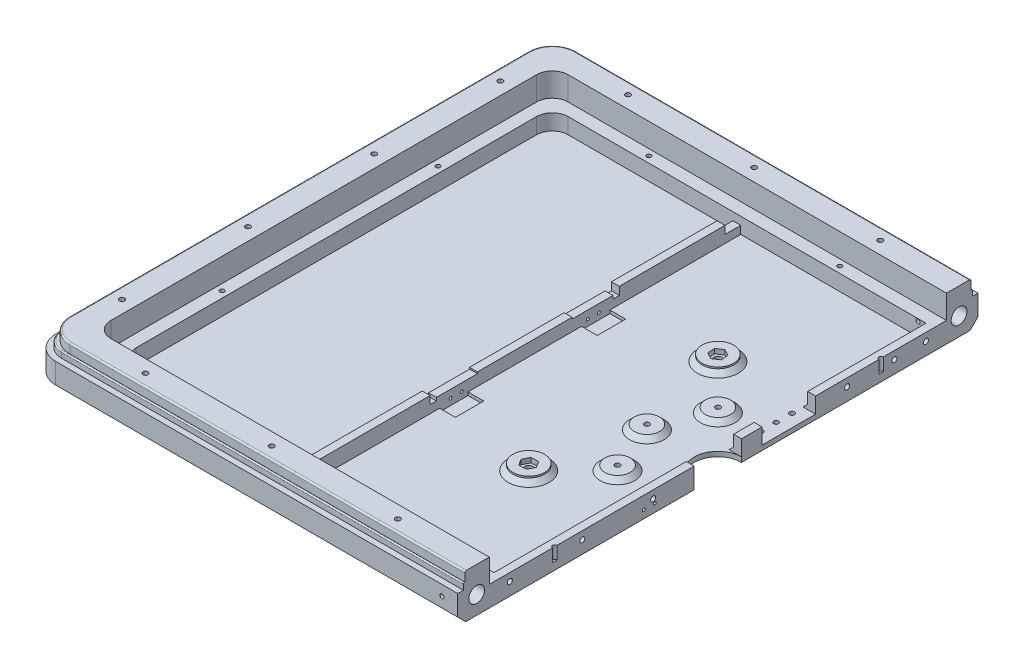
SolidWorks part; units mm, degrees
ref_plane "Front Plane" through (0, 0, 0) normal (0, 0, 1) x (1, 0, 0)
ref_plane "Top Plane" through (0, 0, 0) normal (0, 1, 0) x (1, 0, 0)
ref_plane "Right Plane" through (0, 0, 0) normal (1, 0, 0) x (0, 0, -1)
sketch "Sketch1" plane through (0, 0, 0) normal (0, 1, 0) x (1, 0, 0)
  line L1 (-270, -165) -> (270, -165)
  line L2 (-270, -165) -> (-270, 165)
  line L3 (-270, 165) -> (270, 165)
  line L4 (270, -165) -> (270, 165)
  line L5 (-270, -165) -> (270, 165) construction
  line L6 (-270, 165) -> (270, -165) construction
  point P0 (0, 0)
  dimension "D1" = 540
  dimension "D2" = 330
extrude "Boss-Extrude1" add sketch "Sketch1" along normal blind 3
sketch "Sketch2" plane through (0, 3, 0) normal (0, 1, 0) x (1, 0, 0)
  line L0 (250, 145) -> (-250, 145)
  line L1 (270, -165) -> (-270, -165)
  line L2 (270, -165) -> (270, 165)
  line L3 (270, 165) -> (-270, 165)
  line L4 (-270, -165) -> (-270, 165)
  line L5 (270, -165) -> (-270, 165) construction
  line L6 (270, 165) -> (-270, -165) construction
  line L7 (-250, -145) -> (-250, 145)
  line L8 (250, -145) -> (-250, -145)
  line L9 (250, -145) -> (250, 145)
  point P0 (0, 0)
  dimension "D1" = 20
  dimension "D2" = 540
extrude "Boss-Extrude2" add sketch "Sketch2" along normal blind 25 contours L0 L7 L8 L9 | L2 L1 L4 L3
fillet "Fillet1" radius 15 4 edges at (-270, 14, -165) (-270, 14, 165) (270, 14, 165) (270, 14, -165)
sketch "Sketch4" plane through (0, 28, 0) normal (0, 1, 0) x (1, 0, 0)
  line L0 (-270, 0) -> (-258, 0) construction
  line L1 (-270, -150) -> (-270, 150) construction
  line L2 (-258, 0) -> (-258, 40) construction
  line L3 (-258, 40) -> (-258, 120) construction
  line L4 (0, 0) -> (0, 145) construction
  line L5 (250, 145) -> (-250, 145) construction
  line L6 (0, 165) -> (0, 153) construction
  line L7 (255, 165) -> (-255, 165) construction
  line L8 (0, 153) -> (-50, 153) construction
  line L9 (-50, 153) -> (-130, 153) construction
  line L10 (-130, 153) -> (-210, 153) construction
  line L11 (130, 153) -> (210, 153) construction
  line L12 (50, 153) -> (130, 153) construction
  line L13 (258, 40) -> (258, 120) construction
  line L14 (0, 0) -> (78.1952, 0) construction
  line L15 (258, -40) -> (258, -120) construction
  line L16 (50, -153) -> (130, -153) construction
  line L17 (130, -153) -> (210, -153) construction
  line L18 (-130, -153) -> (-210, -153) construction
  line L19 (-50, -153) -> (-130, -153) construction
  line L20 (0, -153) -> (-50, -153) construction
  line L21 (0, -165) -> (0, -153) construction
  line L22 (-258, -40) -> (-258, -120) construction
  circle A0 centre (-258, 120) radius 1.6
  circle A1 centre (-258, 40) radius 1.6
  circle A2 centre (-210, 153) radius 1.6
  circle A3 centre (-130, 153) radius 1.6
  circle A4 centre (-50, 153) radius 1.6
  circle A5 centre (50, 153) radius 1.6
  circle A6 centre (130, 153) radius 1.6
  circle A7 centre (210, 153) radius 1.6
  circle A8 centre (258, 40) radius 1.6
  circle A9 centre (258, 120) radius 1.6
  circle A10 centre (258, -120) radius 1.6
  circle A11 centre (258, -40) radius 1.6
  circle A12 centre (210, -153) radius 1.6
  circle A13 centre (130, -153) radius 1.6
  circle A14 centre (50, -153) radius 1.6
  circle A15 centre (-50, -153) radius 1.6
  circle A16 centre (-130, -153) radius 1.6
  circle A17 centre (-210, -153) radius 1.6
  circle A18 centre (-258, -40) radius 1.6
  circle A19 centre (-258, -120) radius 1.6
  dimension "D1" = 50
  dimension "D2" = 80
  dimension "D3" = 80
  dimension "D4" = 12
  dimension "D5" = 12
  dimension "D6" = 40
  dimension "D7" = 80
extrude "Cut-Extrude1" cut sketch "Sketch4" against normal up to surface (28 mm away) up to face at (0, 0, 0)
sketch "Sketch5" plane through (0, 3, 0) normal (0, 1, 0) x (1, 0, 0)
  circle A0 centre (0, 0) radius 15
  dimension "D1" = 30
extrude "Cut-Extrude2" cut sketch "Sketch5" against normal up to surface (3 mm away) up to face at (-130, 0, 151.4)
chamfer "Chamfer1" distance 5 angle 45 8 edges at (270, 0, 0) (0, 0, -165) (0, 0, 165) (265.6066, 0, -160.6066) (265.6066, 0, 160.6066) (-265.6066, 0, -160.6066) (-265.6066, 0, 160.6066) (-270, 0, 0)
sketch "Sketch7" plane through (0, 0, 0) normal (0, -1, 0) x (1, 0, 0)
  line L1 (-60, -60) -> (60, -60) construction
  line L2 (-60, -60) -> (-60, 60) construction
  line L3 (-60, 60) -> (60, 60) construction
  line L4 (60, -60) -> (60, 60) construction
  line L5 (-60, -60) -> (60, 60) construction
  line L6 (-60, 60) -> (60, -60) construction
  circle A0 centre (-60, 60) radius 2.6
  circle A1 centre (60, 60) radius 2.6
  circle A2 centre (60, -60) radius 2.6
  circle A3 centre (-60, -60) radius 2.6
  point P0 (0, 0)
  dimension "D1" = 120
  dimension "D2" = 120
extrude "Cut-Extrude3" cut sketch "Sketch7" against normal up to surface (3 mm away) up to face at (0, 3, 15)
sketch "Sketch9" plane through (0, 0, 0) normal (0, -1, 0) x (1, 0, 0)
  line L0 (0, 0) -> (45, 0) construction
  line L1 (-31.8198, -31.8198) -> (31.8198, -31.8198) construction
  line L2 (-31.8198, -31.8198) -> (-31.8198, 31.8198) construction
  line L3 (-31.8198, 31.8198) -> (31.8198, 31.8198) construction
  line L4 (31.8198, -31.8198) -> (31.8198, 31.8198) construction
  line L5 (-31.8198, -31.8198) -> (31.8198, 31.8198) construction
  line L6 (-31.8198, 31.8198) -> (31.8198, -31.8198) construction
  line L7 (0, 0) -> (0, -31.8198) construction
  circle A0 centre (-31.8198, 31.8198) radius 1.6
  circle A1 centre (31.8198, 31.8198) radius 1.6
  circle A2 centre (31.8198, -31.8198) radius 1.6
  circle A3 centre (-31.8198, -31.8198) radius 1.6
  circle A4 centre (45, 0) radius 1.6
  circle A5 centre (-45, 0) radius 1.6
  point P0 (0, 0)
  dimension "D3" = 45
  dimension "D1" = 90
  dimension "D2" = 90
extrude "Cut-Extrude4" cut sketch "Sketch9" against normal blind 47
sketch "Sketch17" plane through (0, 28, 0) normal (0, 1, 0) x (1, 0, 0)
  line L0 (0, 0) -> (0, 165) construction
  line L1 (265, 165) -> (-265, 165) construction
sketch "Sketch18" plane through (0, 28, 0) normal (0, 1, 0) x (1, 0, 0)
  line L0 (0, 165) -> (0, -165) construction
  line L1 (265, 165) -> (-265, 165) construction
  line L2 (265, -165) -> (-265, -165) construction
sketch "Sketch19" plane through (0, 28, 0) normal (0, 1, 0) x (1, 0, 0)
  line L0 (250.5, 160.5) -> (-250.5, 160.5)
  line L1 (255, -165) -> (-255, -165)
  line L2 (270, -150) -> (270, 150)
  line L3 (255, 165) -> (-255, 165)
  line L4 (-270, -150) -> (-270, 150)
  line L5 (270, -165) -> (-270, 165) construction
  line L6 (270, 165) -> (-270, -165) construction
  line L7 (-265.5, -145.5) -> (-265.5, 145.5)
  line L8 (250.5, -160.5) -> (-250.5, -160.5)
  line L9 (265.5, -145.5) -> (265.5, 145.5)
  line L10 (255, 160.5) -> (-255, 160.5) construction
  line L11 (-265.5, -150) -> (-265.5, 150) construction
  line L12 (265.5, -150) -> (265.5, 150) construction
  line L13 (255, -160.5) -> (-255, -160.5) construction
  arc A0 (-270, -150) -> (-255, -165) centre (-255, -150) ccw
  arc A1 (255, -165) -> (270, -150) centre (255, -150) ccw
  arc A2 (270, 150) -> (255, 165) centre (255, 150) ccw
  arc A3 (-255, 165) -> (-270, 150) centre (-255, 150) ccw
  arc A4 (-255, 160.5) -> (-265.5, 150) centre (-255, 150) ccw construction
  arc A5 (-265.5, -150) -> (-255, -160.5) centre (-255, -150) ccw construction
  arc A6 (255, -160.5) -> (265.5, -150) centre (255, -150) ccw construction
  arc A7 (265.5, 150) -> (255, 160.5) centre (255, 150) ccw construction
  arc A8 (-250.5, 160.5) -> (-265.5, 145.5) centre (-250.5, 145.5) ccw
  arc A9 (265.5, 145.5) -> (250.5, 160.5) centre (250.5, 145.5) ccw
  arc A10 (265.5, -145.5) -> (250.5, -160.5) centre (250.5, -145.5) cw
  arc A11 (-250.5, -160.5) -> (-265.5, -145.5) centre (-250.5, -145.5) cw
  point P0 (0, 0)
  dimension "D3" = 15
  dimension "D5" = 15
  dimension "D6" = 15
  dimension "D7" = 15
  dimension "D8" = 15
  dimension "D1" = 330
  dimension "D2" = 540
  dimension "D4" = 4.5
extrude "Cut-Extrude5" cut sketch "Sketch19" against normal blind 10
fillet "Fillet2" radius 1 8 edges at (265.5, 28, 0) (0, 28, 160.5) (-265.5, 28, 0) (0, 28, -160.5) (261.1066, 28, -156.1066) (261.1066, 28, 156.1066) (-261.1066, 28, 156.1066) (-261.1066, 28, -156.1066)
sketch "Sketch20" plane through (0, 18, 0) normal (0, 1, 0) x (1, 0, 0)
  line L0 (0, 165) -> (0, -165) construction
  line L1 (-255, 165) -> (255, 165) construction
  line L2 (-270, 150) -> (-270, -150) construction
  line L3 (-255, -165) -> (255, -165) construction
  line L4 (270, 150) -> (270, -150) construction
  line L5 (-270, 165) -> (270, -165) construction
  line L6 (-270, -165) -> (270, 165) construction
  line L7 (-255, 161.4) -> (255, 161.4)
  line L8 (266.4, 150) -> (266.4, -150)
  line L9 (-255, -161.4) -> (255, -161.4)
  line L10 (-266.4, 150) -> (-266.4, -150)
  line L11 (-255, 157.9) -> (255, 157.9)
  line L12 (262.9, 150) -> (262.9, -150)
  line L13 (-255, -157.9) -> (255, -157.9)
  line L14 (-262.9, 150) -> (-262.9, -150)
  arc A0 (-270, -150) -> (-255, -165) centre (-255, -150) ccw construction
  arc A1 (270, -150) -> (255, -165) centre (255, -150) cw construction
  arc A2 (270, 150) -> (255, 165) centre (255, 150) ccw construction
  arc A3 (-255, 165) -> (-270, 150) centre (-255, 150) ccw construction
  arc A4 (266.4, 150) -> (255, 161.4) centre (255, 150) ccw
  arc A5 (266.4, -150) -> (255, -161.4) centre (255, -150) cw
  arc A6 (-266.4, -150) -> (-255, -161.4) centre (-255, -150) ccw
  arc A7 (-255, 161.4) -> (-266.4, 150) centre (-255, 150) ccw
  arc A8 (262.9, 150) -> (255, 157.9) centre (255, 150) ccw
  arc A9 (262.9, -150) -> (255, -157.9) centre (255, -150) cw
  arc A10 (-262.9, -150) -> (-255, -157.9) centre (-255, -150) ccw
  arc A11 (-255, 157.9) -> (-262.9, 150) centre (-255, 150) ccw
  point P0 (0, 0)
  dimension "D3" = 15
  dimension "D1" = 330
  dimension "D2" = 540
  dimension "D4" = 3.6
  dimension "D5" = 3.5
extrude "Boss-Extrude3" add sketch "Sketch20" along normal blind 4
fillet "Fillet4" radius 0.8 8 edges at (263.061, 22, -158.061) (266.4, 22, 0) (263.061, 22, 158.061) (0, 22, 161.4) (-263.061, 22, 158.061) (-266.4, 22, 0) (-263.061, 22, -158.061) (0, 22, -161.4)
sketch "Sketch23" plane through (0, 3, 0) normal (0, 1, 0) x (1, 0, 0)
  line L0 (250, 145) -> (-250, 145) construction
  line L1 (-5, -145) -> (5, -145)
  line L2 (-5, -145) -> (-5, 145)
  line L3 (-5, 145) -> (5, 145)
  line L4 (5, -145) -> (5, 145)
  line L5 (-5, -145) -> (5, 145) construction
  line L6 (-5, 145) -> (5, -145) construction
  line L7 (0, 0) -> (250, 0) construction
  line L8 (-5, -15) -> (5, -15)
  line L9 (-5, -15) -> (-5, 15)
  line L10 (-5, 15) -> (5, 15)
  line L11 (5, -15) -> (5, 15)
  line L12 (-5, -15) -> (5, 15) construction
  line L13 (-5, 15) -> (5, -15) construction
  line L14 (250, -145) -> (250, 145) construction
  line L15 (250, 145) -> (-250, 145) construction
  line L16 (122.5, -145) -> (127.5, -145)
  line L17 (122.5, -145) -> (122.5, 145)
  line L18 (122.5, 145) -> (127.5, 145)
  line L19 (127.5, -145) -> (127.5, 145)
  line L20 (122.5, -145) -> (127.5, 145) construction
  line L21 (122.5, 145) -> (127.5, -145) construction
  line L27 (0, 0) -> (0, 145) construction
  line L28 (-122.5, 145) -> (-127.5, 145)
  line L29 (-127.5, -145) -> (-127.5, 145)
  line L30 (-122.5, -145) -> (-127.5, -145)
  line L31 (-122.5, -145) -> (-122.5, 145)
  point P0 (0, 0)
  point P8 (0, 0)
  point P17 (125, 0)
  line M14 (-250, -145) -> (250, -145)
  line M16 (250, 145) -> (-250, 145)
  dimension "D1" = 30
  dimension "D2" = 10
  dimension "D3" = 5
extrude "Boss-Extrude4" add sketch "Sketch23" along normal blind 10 contours L2 L10 L4 M16 | L8 L2 L4 M14 | L17 L16 L19 L18 | L28 L29 L30 L31 region at (0, 3, 80) region at (0, 3, -80)
sketch "Sketch24" plane through (0, 3, 0) normal (0, 1, 0) x (1, 0, 0)
  line L0 (-242, 137) -> (242, 137)
  line L1 (-250, -145) -> (250, -145)
  line L2 (-250, -145) -> (-250, 145)
  line L3 (-250, 145) -> (250, 145)
  line L4 (250, -145) -> (250, 145)
  line L5 (-250, -145) -> (250, 145) construction
  line L6 (-250, 145) -> (250, -145) construction
  line L7 (242, -137) -> (242, 137)
  line L8 (-242, -137) -> (242, -137)
  line L9 (-242, -137) -> (-242, 137)
  point P0 (0, 0)
  dimension "D1" = 8
extrude "Boss-Extrude5" add sketch "Sketch24" along normal up to surface (10 mm away) up to face at (-125, 13, 0)
sketch "Sketch25" plane through (127.5, 0, 0) normal (1, 0, 0) x (0, 0, -1)
  line L0 (0, 5) -> (0, 13) construction
  line L1 (-150, 5) -> (150, 5) construction
  line L2 (-145, 13) -> (145, 13) construction
  line L3 (0, 13) -> (0, 5) construction
  line L4 (0, 5) -> (-40, 5) construction
  line L5 (-40, 5) -> (-47, 5) construction
  circle A0 centre (-47, 5) radius 0.9
  circle A1 centre (-40, 5) radius 0.9
  circle A2 centre (47, 5) radius 0.9
  circle A3 centre (40, 5) radius 0.9
  dimension "D1" = 8
  dimension "D2" = 40
  dimension "D3" = 7
extrude "Cut-Extrude6" cut sketch "Sketch25" against normal up to surface (255 mm away) up to face at (-127.5, 8, 0)
sketch "Sketch26" plane through (0, 3, 0) normal (0, 1, 0) x (1, 0, 0)
  line L0 (0, 0) -> (-122.5, 0) construction
  line L1 (-122.5, -137) -> (-122.5, 137) construction
  line L2 (-122.5, 0) -> (-122.5, 36) construction
  line L3 (-122.5, -137) -> (-122.5, 137) construction
  line L4 (-122.5, -54) -> (-112.5, -54)
  line L5 (-122.5, 36) -> (-112.5, 36)
  line L6 (-122.5, 36) -> (-122.5, 54)
  line L7 (-122.5, 54) -> (-112.5, 54)
  line L8 (-112.5, 36) -> (-112.5, 54)
  line L9 (-122.5, -36) -> (-112.5, -36)
  line L10 (-122.5, -36) -> (-122.5, -54)
  line L11 (-112.5, -36) -> (-112.5, -54)
  line L12 (0, 0) -> (0, 165) construction
  line L13 (122.5, -36) -> (122.5, -54)
  line L14 (122.5, -36) -> (112.5, -36)
  line L15 (112.5, -36) -> (112.5, -54)
  line L16 (122.5, -54) -> (112.5, -54)
  line L17 (122.5, 54) -> (112.5, 54)
  line L18 (112.5, 36) -> (112.5, 54)
  line L19 (122.5, 36) -> (112.5, 36)
  line L20 (122.5, 36) -> (122.5, 54)
  point P11 (-112.5, 45)
  dimension "D1" = 36
  dimension "D2" = 10
extrude "Cut-Extrude7" cut sketch "Sketch26" against normal blind 2
sketch "Sketch27" plane through (0, 13, 0) normal (0, 1, 0) x (1, 0, 0)
  line L0 (0, 0) -> (0, 165) construction
  line L1 (-122.5, 0) -> (-127.5, 0) construction
  line L2 (-122.5, -36) -> (-122.5, 36) construction
  line L3 (-127.5, -137) -> (-127.5, 137) construction
  line L4 (-127.5, -137) -> (-127.5, 137) construction
  line L5 (-122.5, -60) -> (-127.5, -60)
  line L6 (-122.5, -60) -> (-122.5, -30)
  line L7 (-122.5, 60) -> (-127.5, 60)
  line L8 (-127.5, -60) -> (-127.5, -30)
  line L9 (-122.5, -60) -> (-123.75, -30) construction
  line L10 (-122.5, 60) -> (-123.75, 30) construction
  line L11 (-127.5, 30) -> (-127.5, 60)
  line L12 (-127.5, -30) -> (-122.5, -30)
  line L14 (-127.5, 30) -> (-122.5, 30)
  line L16 (126.25, -30) -> (127.5, -60) construction
  line L17 (126.25, 30) -> (127.5, 60) construction
  line L18 (-126.25, 30) -> (-127.5, 60) construction
  line L19 (-126.25, -30) -> (-127.5, -60) construction
  line L20 (-122.5, 30) -> (-122.5, 60)
  line L21 (122.5, 60) -> (123.75, 30) construction
  line L22 (122.5, -60) -> (123.75, -30) construction
  line L23 (122.5, 0) -> (127.5, 0) construction
  line L24 (122.5, 30) -> (122.5, 60)
  line L25 (127.5, 30) -> (122.5, 30)
  line L26 (127.5, -30) -> (122.5, -30)
  line L27 (127.5, 30) -> (127.5, 60)
  line L28 (127.5, -60) -> (127.5, -30)
  line L29 (122.5, 60) -> (127.5, 60)
  line L30 (122.5, -60) -> (122.5, -30)
  line L31 (122.5, -60) -> (127.5, -60)
  point P10 (-125, 0)
  point P17 (-125, 0)
  point P40 (125, 0)
  dimension "D1" = 120
  dimension "D2" = 60
extrude "Cut-Extrude8" cut sketch "Sketch27" against normal blind 3
sketch "Sketch28" plane through (0, 13, 0) normal (0, 1, 0) x (1, 0, 0)
  line L1 (-127.5, 30) -> (-122.5, 30)
  line L2 (-127.5, 30) -> (-127.5, -30)
  line L3 (-127.5, -30) -> (-122.5, -30)
  line L4 (-122.5, 30) -> (-122.5, -30)
  line L5 (122.5, 30) -> (127.5, 30)
  line L6 (122.5, 30) -> (122.5, -30)
  line L7 (122.5, -30) -> (127.5, -30)
  line L8 (127.5, 30) -> (127.5, -30)
extrude "Cut-Extrude9" cut sketch "Sketch28" against normal blind 2
sketch "Sketch29" plane through (0, 10, 0) normal (0, 1, 0) x (1, 0, 0)
  line L0 (-122.5, 30) -> (-122.5, 60) construction
  line L1 (-127.5, 60) -> (-122.5, 60)
  line L2 (-127.5, 60) -> (-127.5, 56)
  line L3 (-127.5, 56) -> (-122.5, 56)
  line L4 (-122.5, 60) -> (-122.5, 56)
  line L5 (-122.5, -60) -> (-122.5, -30) construction
  line L6 (-127.5, -60) -> (-122.5, -60)
  line L7 (-127.5, -60) -> (-127.5, -56)
  line L8 (-127.5, -56) -> (-122.5, -56)
  line L9 (-122.5, -60) -> (-122.5, -56)
  line L10 (127.5, -60) -> (127.5, -30) construction
  line L11 (122.5, -60) -> (127.5, -60)
  line L12 (122.5, -60) -> (122.5, -56)
  line L13 (122.5, -56) -> (127.5, -56)
  line L14 (127.5, -60) -> (127.5, -56)
  line L15 (127.5, -137) -> (127.5, 137) construction
  line L16 (122.5, 60) -> (127.5, 60)
  line L17 (122.5, 60) -> (122.5, 56)
  line L18 (122.5, 56) -> (127.5, 56)
  line L19 (127.5, 60) -> (127.5, 56)
extrude "Cut-Extrude10" cut sketch "Sketch29" against normal blind 2
sketch "Sketch31" plane through (0, 13, 0) normal (0, 1, 0) x (1, 0, 0)
  line L0 (0, 165) -> (0, 45) construction
  line L1 (255, 165) -> (-255, 165) construction
  line L3 (-8, 62) -> (8, 62)
  line L4 (-8, 62) -> (-8, 28)
  line L5 (-8, 28) -> (8, 28)
  line L6 (8, 62) -> (8, 28)
  line L7 (-8, 62) -> (8, 28) construction
  line L8 (-8, 28) -> (8, 62) construction
  dimension "D1" = 120
  dimension "D2" = 34
  dimension "D3" = 16
  dimension "D4" = 16
sketch "Sketch32" plane through (-270, 0, 0) normal (-1, 0, 0) x (0, 0, 1)
  line L0 (-30, 13) -> (-30, 18) construction
  line L1 (-62, 13) -> (-28, 13) construction
  line L2 (-150, 18) -> (150, 18) construction
  line L3 (-30, 18) -> (-30, 51) construction
extrude "Boss-Extrude6" add sketch "Sketch31" along normal blind 53 and the other way up to surface (10 mm away) other way up to face at (-60, 3, 57.4)
fillet "Fillet5" radius 15 2 edges at (0, 66, -28) (0, 66, -62)
sketch "Sketch34" plane through (-8, 0, 0) normal (-1, 0, 0) x (0, 0, 1)
  line L0 (-165, 18) -> (-45, 18) construction
  line L1 (-150, 18) -> (150, 18) construction
  line L2 (-45, 18) -> (-45, 53) construction
  circle A0 centre (-45, 53) radius 3
  dimension "D3" = 6
  dimension "D1" = 120
  dimension "D2" = 35
extrude "Cut-Extrude11" cut sketch "Sketch34" against normal blind 53
sketch "Sketch35" plane through (0, 3, 0) normal (0, 1, 0) x (1, 0, 0)
  circle A0 centre (-31.8198, 31.8198) radius 1.6
  circle A1 centre (-31.8198, 31.8198) radius 8
  circle A2 centre (31.8198, 31.8198) radius 1.6
  circle A3 centre (31.8198, 31.8198) radius 8
  circle A4 centre (31.8198, -31.8198) radius 1.6
  circle A5 centre (31.8198, -31.8198) radius 8
  circle A6 centre (-31.8198, -31.8198) radius 1.6
  circle A7 centre (-31.8198, -31.8198) radius 8
  circle A8 centre (-45, 0) radius 8
  circle A9 centre (45, 0) radius 8
  circle A10 centre (45, 0) radius 1.6
  circle A11 centre (-45, 0) radius 1.6
  point P16 (0, 0)
  dimension "D1" = 16
  dimension "D2" = 3.2
  dimension "D3" = 4
extrude "Boss-Extrude7" add sketch "Sketch35" along normal blind 3
chamfer "Chamfer2" distance 3 angle 45 6 edges at (31.8198, 3, 23.8198) (-31.8198, 3, 23.8198) (-31.8198, 3, -39.8198) (31.8198, 3, -39.8198) (45, 3, -8) (-45, 3, -8)
sketch "Sketch37" plane through (0, 66, 0) normal (0, 1, 0) x (1, 0, 0)
  line L0 (0, 47) -> (0, 43) construction
  line L1 (8, 47) -> (-8, 47) construction
  line L2 (-8, 43) -> (8, 43) construction
  line L4 (-8, 28) -> (8, 28)
  line L5 (-8, 28) -> (-8, 62)
  line L6 (-8, 62) -> (8, 62)
  line L7 (8, 28) -> (8, 62)
  line L8 (-8, 28) -> (8, 62) construction
  line L9 (-8, 62) -> (8, 28) construction
  point P6 (0, 45)
extrude "Cut-Extrude12" cut sketch "Sketch37" against normal up to surface (63 mm away) up to face at (-45, 3, -11)
sketch "Sketch38" plane through (0, 3, 0) normal (0, 1, 0) x (1, 0, 0)
  line L0 (0, 62) -> (0, 28) construction
  line L1 (5, 62) -> (-5, 62) construction
  line L2 (-5, 28) -> (5, 28) construction
  line L3 (0, 28) -> (0, 45) construction
  line L4 (0, 45) -> (8, 45) construction
  line L5 (8, 45) -> (8, 55) construction
  circle A0 centre (8, 55) radius 1.6
  circle A1 centre (8, 35) radius 1.6
  circle A2 centre (-8, 35) radius 1.6
  circle A3 centre (-8, 55) radius 1.6
  circle A4 centre (8, 45) radius 1.5
  circle A5 centre (-8, 45) radius 1.5
  dimension "D2" = 10
  dimension "D1" = 8
extrude "Cut-Extrude13" cut sketch "Sketch38" against normal blind 90
chamfer "Chamfer3" distance 3 angle 45 6 edges at (-5, 3, 76) (-5, 3, -21.5) (5, 3, -21.5) (5, 3, 76) (5, 3, -99.5) (-5, 3, -99.5)
sketch "Sketch39" plane through (0, 13, 0) normal (0, 1, 0) x (1, 0, 0)
  line L0 (-242, 0) -> (-242, 137) construction
  line L1 (-242, 137) -> (-242, -137) construction
  line L2 (-242, 137) -> (-242, 68.5) construction
  line L3 (-242, 68.5) -> (-250, 68.5) construction
  line L4 (-250, -145) -> (-250, 145) construction
  line L5 (-184.75, 137) -> (-184.75, 145) construction
  line L6 (-127.5, 137) -> (-242, 137) construction
  line L7 (250, 145) -> (-250, 145) construction
  line L8 (-63.75, 137) -> (-63.75, 145) construction
  line L10 (-5, 137) -> (-122.5, 137) construction
  line L11 (250, 145) -> (-250, 145) construction
  line L12 (0, 0) -> (0, 145) construction
  line L13 (63.75, 137) -> (63.75, 145) construction
  line L14 (184.75, 137) -> (184.75, 145) construction
  line L15 (242, 68.5) -> (250, 68.5) construction
  line L16 (242, 137) -> (242, 68.5) construction
  line L17 (0, 62) -> (0, 145) construction
  line L18 (5, 62) -> (-5, 62) construction
  line L19 (0, 0) -> (250, 0) construction
  line L20 (250, -145) -> (250, 145) construction
  line L21 (0, -62) -> (0, -145) construction
  line L22 (242, -137) -> (242, -68.5) construction
  line L23 (242, -68.5) -> (250, -68.5) construction
  line L24 (184.75, -137) -> (184.75, -145) construction
  line L25 (63.75, -137) -> (63.75, -145) construction
  line L26 (-63.75, -137) -> (-63.75, -145) construction
  line L27 (-184.75, -137) -> (-184.75, -145) construction
  line L28 (-242, -68.5) -> (-250, -68.5) construction
  line L29 (-242, -137) -> (-242, -68.5) construction
  circle A0 centre (-246, 68.5) radius 1.4
  circle A1 centre (-184.75, 141) radius 1.4
  circle A2 centre (-63.75, 141) radius 1.4
  circle A3 centre (63.75, 141) radius 1.4
  circle A4 centre (184.75, 141) radius 1.4
  circle A5 centre (246, 68.5) radius 1.4
  circle A6 centre (0, 103.5) radius 1.4
  circle A7 centre (0, -103.5) radius 1.4
  circle A8 centre (246, -68.5) radius 1.4
  circle A9 centre (184.75, -141) radius 1.4
  circle A10 centre (63.75, -141) radius 1.4
  circle A11 centre (-63.75, -141) radius 1.4
  circle A12 centre (-184.75, -141) radius 1.4
  circle A13 centre (-246, -68.5) radius 1.4
extrude "Cut-Extrude14" cut sketch "Sketch39" against normal blind 8
fillet "Fillet6" radius 10 4 edges at (-242, 8, -137) (-242, 8, 137) (242, 8, 137) (242, 8, -137)
fillet "Fillet7" radius 10 4 edges at (250, 20.5, 145) (250, 20.5, -145) (-250, 20.5, 145) (-250, 20.5, -145)
sketch "Sketch41" plane through (0, 0, 0) normal (1, 0, 0) x (0, 0, -1)
  line L0 (165, 11.5) -> (153, 11.5) construction
  line L1 (165, 18) -> (165, 5) construction
  line L2 (0, 0) -> (0, 98.4706) construction
  circle A0 centre (153, 11.5) radius 5
  circle A1 centre (-153, 11.5) radius 5
  dimension "D1" = 12
extrude "Cut-Extrude15" cut sketch "Sketch41" against normal blind 30 and the other way blind 30
sketch "Sketch42" plane through (5, 0, 0) normal (1, 0, 0) x (0, 0, -1)
  line L0 (-132, 3) -> (-132, 13) construction
  line L1 (-127, 3) -> (-137, 3) construction
  line L2 (-135, 13) -> (135, 13) construction
  line L3 (-102.1, 13) -> (-69.9, 13) construction
  line L4 (-69.9, 13) -> (-86, 13) construction
  line L5 (-86, 13) -> (-86, 3) construction
  line L6 (-127, 3) -> (127, 3) construction
  line L7 (-67.1, 13) -> (-15, 13) construction
  line L8 (-15, 13) -> (-41.05, 13) construction
  line L9 (-41.05, 13) -> (-41.05, 3) construction
  line L10 (145, 13) -> (145, 3) construction
  line L11 (145, 3) -> (145, 8) construction
  line L12 (145, 8) -> (132, 8) construction
  line L13 (132, 8) -> (112, 8) construction
  line L14 (112, 8) -> (82, 8) construction
  circle A0 centre (112, 8) radius 1.6
  circle A1 centre (132, 8) radius 1.6
  circle A2 centre (82, 8) radius 1.6
  circle A3 centre (-86, 8) radius 1.6
  circle A4 centre (-132, 8) radius 1.6
  circle A5 centre (-41.05, 8) radius 1.6
  dimension "D1" = 30
  dimension "D2" = 20
  dimension "D3" = 13
extrude "Cut-Extrude16" cut sketch "Sketch42" against normal blind 30 and the other way blind 10
sketch "Sketch43" plane through (5, 0, 0) normal (1, 0, 0) x (0, 0, -1)
  line L0 (-87.6166, 10.8) -> (-89.2332, 8)
  line L1 (-128.7668, 8) -> (-130.3834, 10.8)
  line L2 (-130.3834, 10.8) -> (-133.6166, 10.8)
  line L3 (-133.6166, 10.8) -> (-135.2332, 8)
  line L4 (-135.2332, 8) -> (-133.6166, 5.2)
  line L5 (-133.6166, 5.2) -> (-130.3834, 5.2)
  line L6 (-130.3834, 5.2) -> (-128.7668, 8)
  line L7 (-89.2332, 8) -> (-87.6166, 5.2)
  line L8 (-87.6166, 5.2) -> (-84.3834, 5.2)
  line L9 (-82.7668, 8) -> (-84.3834, 10.8)
  line L10 (-84.3834, 10.8) -> (-87.6166, 10.8)
  line L11 (-84.3834, 5.2) -> (-82.7668, 8)
  line L12 (-37.8168, 8) -> (-39.4334, 10.8)
  line L13 (-39.4334, 5.2) -> (-37.8168, 8)
  line L14 (-42.6666, 10.8) -> (-44.2832, 8)
  line L15 (-39.4334, 10.8) -> (-42.6666, 10.8)
  line L16 (-42.6666, 5.2) -> (-39.4334, 5.2)
  line L17 (-44.2832, 8) -> (-42.6666, 5.2)
  line L18 (85.2332, 8) -> (83.6166, 10.8)
  line L19 (83.6166, 5.2) -> (85.2332, 8)
  line L20 (80.3834, 10.8) -> (78.7668, 8)
  line L21 (83.6166, 10.8) -> (80.3834, 10.8)
  line L22 (80.3834, 5.2) -> (83.6166, 5.2)
  line L23 (78.7668, 8) -> (80.3834, 5.2)
  line L24 (115.2332, 8) -> (113.6166, 10.8)
  line L25 (113.6166, 5.2) -> (115.2332, 8)
  line L26 (110.3834, 10.8) -> (108.7668, 8)
  line L27 (113.6166, 10.8) -> (110.3834, 10.8)
  line L28 (110.3834, 5.2) -> (113.6166, 5.2)
  line L29 (108.7668, 8) -> (110.3834, 5.2)
  line L30 (82, 8) -> (112, 8) construction
  line L31 (112, 8) -> (132, 8) construction
  line L32 (130.3834, 10.8) -> (128.7668, 8)
  line L33 (130.3834, 5.2) -> (133.6166, 5.2)
  line L34 (135.2332, 8) -> (133.6166, 10.8)
  line L35 (133.6166, 10.8) -> (130.3834, 10.8)
  line L36 (128.7668, 8) -> (130.3834, 5.2)
  line L37 (133.6166, 5.2) -> (135.2332, 8)
  circle A0 centre (-132, 8) radius 2.8 construction
  circle A1 centre (-86, 8) radius 2.8 construction
  circle A2 centre (-41.05, 8) radius 2.8 construction
  circle A3 centre (82, 8) radius 2.8 construction
  circle A4 centre (112, 8) radius 2.8 construction
  circle A5 centre (132, 8) radius 2.8 construction
  dimension "D1" = 5.6
extrude "Cut-Extrude17" cut sketch "Sketch43" against normal blind 2 and the other way blind 17
sketch "Sketch45" plane through (0, 3, 0) normal (0, 1, 0) x (1, 0, 0)
  circle A0 centre (-60, 60) radius 10
  circle A1 centre (-60, 60) radius 2.6
  circle A2 centre (60, 60) radius 10
  circle A3 centre (60, 60) radius 2.6
  circle A4 centre (60, -60) radius 10
  circle A5 centre (60, -60) radius 2.6
  circle A6 centre (-60, -60) radius 10
  circle A7 centre (-60, -60) radius 2.6
  point P16 (0, 0)
  dimension "D1" = 20
  dimension "D2" = 4
extrude "Boss-Extrude8" add sketch "Sketch45" along normal blind 4
chamfer "Chamfer4" distance 3 angle 45 4 edges at (-60, 3, -70) (60, 3, -70) (-60, 3, 50) (60, 3, 50)
sketch "Sketch48" plane through (0, 7, 0) normal (0, 1, 0) x (1, 0, 0)
  line L0 (62.567, 56.091) -> (64.6688, 60.2686)
  line L1 (-56.091, 62.567) -> (-60.2686, 64.6688)
  line L2 (-60.2686, 64.6688) -> (-64.1776, 62.1018)
  line L3 (-64.1776, 62.1018) -> (-63.909, 57.433)
  line L4 (-63.909, 57.433) -> (-59.7314, 55.3312)
  line L5 (-59.7314, 55.3312) -> (-55.8224, 57.8982)
  line L6 (-55.8224, 57.8982) -> (-56.091, 62.567)
  line L7 (64.6688, 60.2686) -> (62.1018, 64.1776)
  line L8 (62.1018, 64.1776) -> (57.433, 63.909)
  line L9 (57.433, 63.909) -> (55.3312, 59.7314)
  line L10 (55.3312, 59.7314) -> (57.8982, 55.8224)
  line L11 (57.8982, 55.8224) -> (62.567, 56.091)
  line L12 (56.091, -62.567) -> (60.2686, -64.6688)
  line L13 (60.2686, -64.6688) -> (64.1776, -62.1018)
  line L14 (64.1776, -62.1018) -> (63.909, -57.433)
  line L15 (63.909, -57.433) -> (59.7314, -55.3312)
  line L16 (59.7314, -55.3312) -> (55.8224, -57.8982)
  line L17 (55.8224, -57.8982) -> (56.091, -62.567)
  line L18 (-62.567, -56.091) -> (-64.6688, -60.2686)
  line L19 (-64.6688, -60.2686) -> (-62.1018, -64.1776)
  line L20 (-62.1018, -64.1776) -> (-57.433, -63.909)
  line L21 (-57.433, -63.909) -> (-55.3312, -59.7314)
  line L22 (-55.3312, -59.7314) -> (-57.8982, -55.8224)
  line L23 (-57.8982, -55.8224) -> (-62.567, -56.091)
  circle A0 centre (-60, 60) radius 4.05 construction
  circle A1 centre (60, 60) radius 4.05 construction
  circle A2 centre (60, -60) radius 4.05 construction
  circle A3 centre (-60, -60) radius 4.05 construction
  point P36 (0, 0)
  dimension "D1" = 8.1
  dimension "D2" = 4
extrude "Cut-Extrude18" cut sketch "Sketch48" against normal blind 3
sketch "Sketch49" plane through (0, 0, 0) normal (0, -1, 0) x (1, 0, 0)
  circle A0 centre (0, 0) radius 60
sketch "Sketch50" plane through (0, 0, 0) normal (0, -1, 0) x (1, 0, 0)
  line L1 (-60, 60) -> (60, 60) construction
sketch "Sketch52" plane through (0, 0, 165) normal (0, 0, 1) x (1, 0, 0)
  line L0 (0, 5) -> (0, 18) construction
  line L1 (-255, 5) -> (255, 5) construction
  line L2 (-255, 18) -> (255, 18) construction
  line L3 (0, 18) -> (0, 11.5) construction
  line L4 (0, 11.5) -> (-10, 11.5) construction
  circle A0 centre (-10, 11.5) radius 1.35
  circle A1 centre (10, 11.5) radius 1.35
  dimension "D2" = 2.7
  dimension "D1" = 10
extrude "Cut-Extrude20" cut sketch "Sketch52" against normal up to surface (330 mm away) contours A0 | A1 region at (-10, 11.5, 165) up to face at (0, 11.5, -165)
sketch "Sketch51" plane through (0, 28, 0) normal (0, 1, 0) x (1, 0, 0)
  line L0 (0, 0) -> (0, 165) construction
  line L1 (255, 165) -> (-255, 165) construction
  line L3 (0, 165) -> (369.7515, 165)
  line L4 (0, 165) -> (0, -203.5915)
  line L5 (0, -203.5915) -> (369.7515, -203.5915)
  line L6 (369.7515, 165) -> (369.7515, -203.5915)
extrude "Cut-Extrude21" cut sketch "Sketch51" against normal up to surface (28 mm away) up to face at (8, 0, -36.6)
sketch "Sketch53" plane through (0, 13, 0) normal (0, 1, 0) x (1, 0, 0)
  line L0 (-122.5, 60) -> (-122.5, 137) construction
  line L1 (-127.5, 137) -> (-122.5, 137)
  line L2 (-127.5, 137) -> (-127.5, 127)
  line L3 (-127.5, 127) -> (-122.5, 127)
  line L4 (-122.5, 137) -> (-122.5, 127)
extrude "Cut-Extrude22" cut sketch "Sketch53" against normal blind 5
